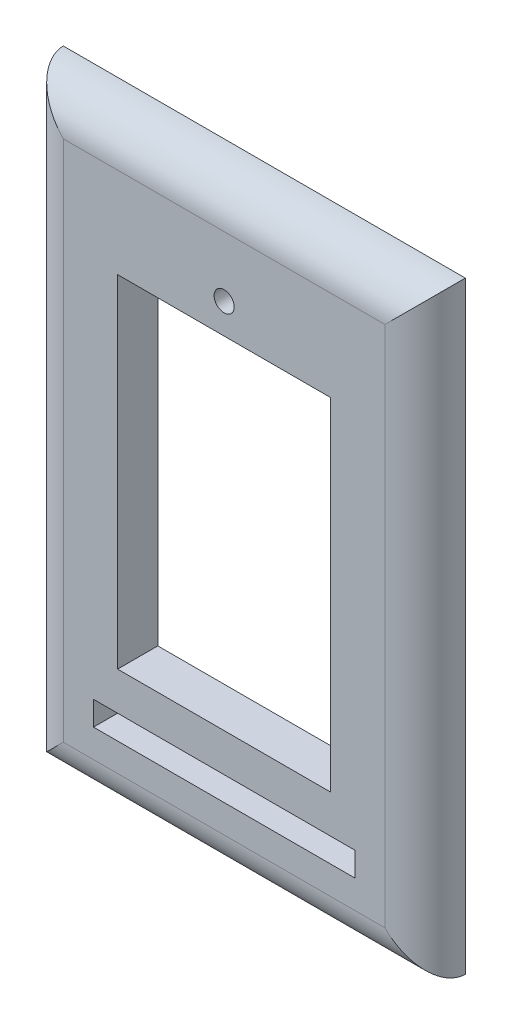
SolidWorks part; units mm, degrees
ref_plane "Front Plane" through (0, 0, 0) normal (0, 0, 1) x (1, 0, 0)
ref_plane "Top Plane" through (0, 0, 0) normal (0, 1, 0) x (1, 0, 0)
ref_plane "Right Plane" through (0, 0, 0) normal (1, 0, 0) x (0, 0, -1)
sketch "Sketch2" plane through (0, 0, 0) normal (0, 0, 1) x (1, 0, 0)
  line L1 (50, -75) -> (-50, -75)
  line L2 (50, -75) -> (50, 75)
  line L3 (50, 75) -> (-50, 75)
  line L4 (-50, -75) -> (-50, 75)
  line L5 (50, -75) -> (-50, 75) construction
  line L6 (50, 75) -> (-50, -75) construction
  point P0 (0, 0)
  dimension "D1" = 150
  dimension "D2" = 100
extrude "Boss-Extrude1" add sketch "Sketch2" along normal blind 10
fillet "Fillet1" radius 10 4 edges at (-50, 0, 10) (0, -75, 10) (50, 0, 10) (0, 75, 10) type face fillet first side face at (0, 0, 10) second side face at (0, 75, 5) second side face at (50, 0, 5) second side face at (0, -75, 5) second side face at (-50, 0, 5)
sketch "Sketch3" plane through (0, 0, 10) normal (0, 0, 1) x (1, 0, 0)
  line L0 (0, 0) -> (0, 50) construction
  circle A0 centre (0, 50) radius 2.5
  dimension "D2" = 5
  dimension "D1" = 50
extrude "Cut-Extrude1" cut sketch "Sketch3" against normal blind 10
sketch "Sketch4" plane through (0, 0, 10) normal (0, 0, 1) x (1, 0, 0)
  line L1 (26.5, -42.5) -> (-26.5, -42.5)
  line L2 (26.5, -42.5) -> (26.5, 42.5)
  line L3 (26.5, 42.5) -> (-26.5, 42.5)
  line L4 (-26.5, -42.5) -> (-26.5, 42.5)
  line L5 (26.5, -42.5) -> (-26.5, 42.5) construction
  line L6 (26.5, 42.5) -> (-26.5, -42.5) construction
  point P0 (0, 0)
  dimension "D1" = 53
  dimension "D2" = 85
extrude "Cut-Extrude2" cut sketch "Sketch4" against normal blind 10
sketch "Sketch5" plane through (0, 0, 10) normal (0, 0, 1) x (1, 0, 0)
  line L0 (0, 0) -> (0, -55) construction
  line L2 (32.5, -58) -> (-32.5, -58)
  line L3 (32.5, -58) -> (32.5, -52)
  line L4 (32.5, -52) -> (-32.5, -52)
  line L5 (-32.5, -58) -> (-32.5, -52)
  line L6 (32.5, -58) -> (-32.5, -52) construction
  line L7 (32.5, -52) -> (-32.5, -58) construction
  dimension "D1" = 55
  dimension "D2" = 65
  dimension "D3" = 6
extrude "Cut-Extrude3" cut sketch "Sketch5" against normal blind 10
